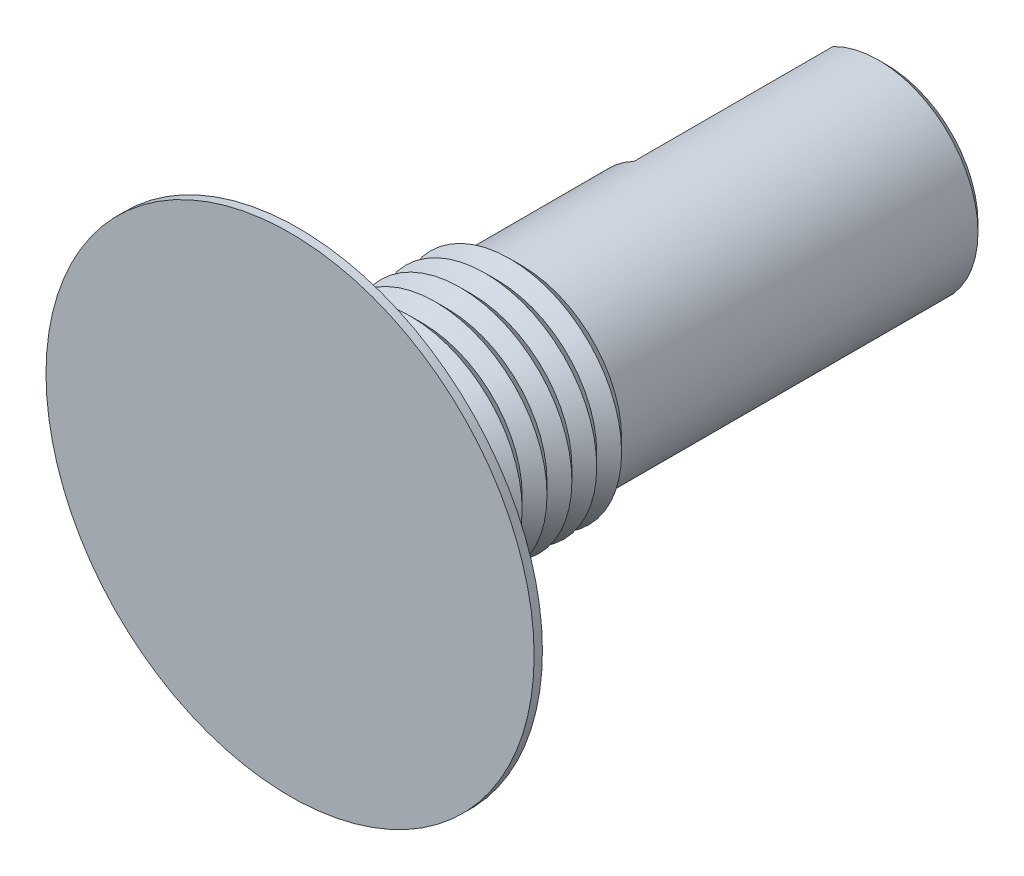
SolidWorks part; units mm, degrees
ref_plane "Front Plane" through (0, 0, 0) normal (0, 0, 1) x (1, 0, 0)
ref_plane "Top Plane" through (0, 0, 0) normal (0, 1, 0) x (1, 0, 0)
ref_plane "Right Plane" through (0, 0, 0) normal (1, 0, 0) x (0, 0, -1)
sketch "Sketch1" plane through (0, 0, 0) normal (0, 0, 1) x (1, 0, 0)
  circle A0 centre (0, 0) radius 7.4797
extrude "Boss-Extrude1" add sketch "Sketch1" along normal blind 0.254
sketch "Sketch2" plane through (0, 0, 0) normal (0, 0, -1) x (-1, 0, 0)
  circle A0 centre (0, 0) radius 3.429
extrude "Boss-Extrude2" add sketch "Sketch2" along normal blind 0.762 separate body
chamfer "Chamfer1" distance 0.381 angle 45 2 edges at (-3.429, 0, -0.762) (-3.429, 0, 0)
pattern_linear "LPattern3" count 9 spacing 0.762 along (0, 0, -1) of bodies 102
sketch "Sketch3" plane through (0, 0, -6.858) normal (0, 0, -1) x (-1, 0, 0)
  circle A1 centre (0, 0) radius 3.048
  circle A2 centre (0, 0) radius 3.048
  dimension "D1" = 0
extrude "Boss-Extrude3" add sketch "Sketch3" along normal blind 11.176
sketch "Sketch4" plane through (0, 0, -18.034) normal (0, 0, -1) x (-1, 0, 0)
  line L0 (1.397, 2.709) -> (1.397, -2.709)
  circle A1 centre (0, 0) radius 3.048
  arc A2 (1.397, -2.709) -> (1.397, 2.709) centre (0, 0) ccw
  dimension "D2" = 4.445
  dimension "D1" = 0
extrude "Cut-Extrude1" cut sketch "Sketch4" against normal blind 6.35
chamfer "Chamfer2" distance 0.254 angle 45 1 edges at (3.048, 0, -18.034)
